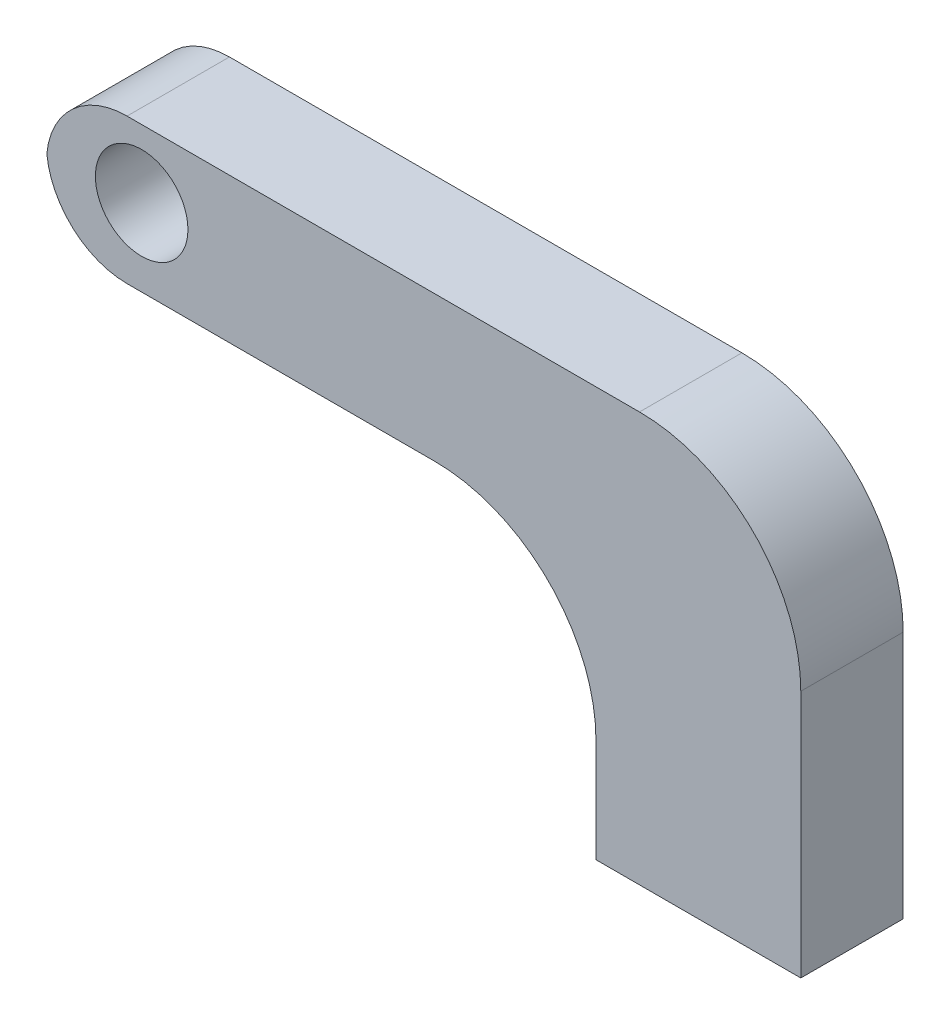
SolidWorks part; units mm, degrees
ref_plane "Front Plane" through (0, 0, 0) normal (0, 0, 1) x (1, 0, 0)
ref_plane "Top Plane" through (0, 0, 0) normal (0, 1, 0) x (1, 0, 0)
ref_plane "Right Plane" through (0, 0, 0) normal (1, 0, 0) x (0, 0, -1)
sketch "Sketch1" plane through (0, 0, 0) normal (0, 0, 1) x (1, 0, 0)
  line L1 (-12.7, 38.1) -> (-25.4, 38.1)
  line L2 (-12.7, 38.1) -> (-12.7, 44.45)
  line L4 (-25.4, 38.1) -> (-25.4, 44.45)
  line L5 (-59.4811, 63.5) -> (-12.7, 63.5)
  line L6 (-59.4811, 63.5) -> (-59.4811, 54.5)
  line L7 (-59.4811, 54.5) -> (-25.4, 54.5)
  line L8 (-12.7, 63.5) -> (-12.7, 54.4246)
  line L10 (-12.7, 54.4246) -> (-12.7, 44.45)
  line L12 (-25.4, 54.5) -> (-25.4, 44.45)
  circle A0 centre (-53.575, 59.2899) radius 2.8702
  dimension "D1" = 25.4
  dimension "D2" = 9
extrude "Boss-Extrude1" add sketch "Sketch1" along normal blind 6.35
fillet "Fillet1" radius 10 2 edges at (-12.7, 63.5, 3.175) (-25.4, 54.5, 3.175)
fillet "Fillet2" radius 5 2 edges at (-59.4811, 63.5, 3.175) (-59.4811, 54.5, 3.175)
